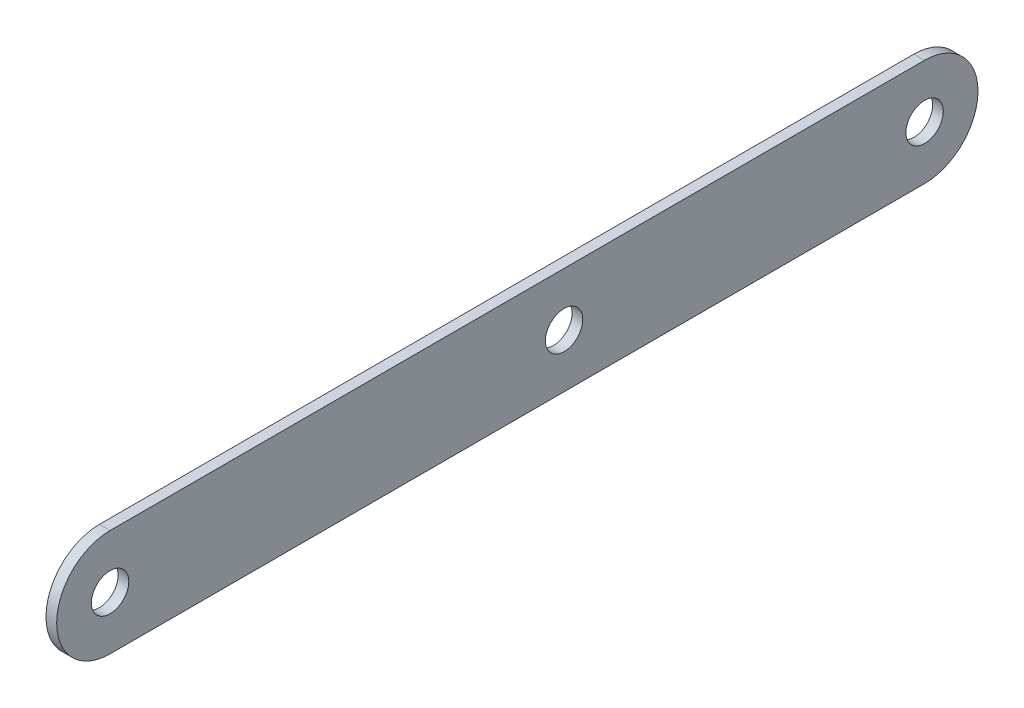
SolidWorks part; units mm, degrees
ref_plane "Спереди" through (0, 0, 0) normal (0, 0, 1) x (1, 0, 0)
ref_plane "Сверху" through (0, 0, 0) normal (0, 1, 0) x (1, 0, 0)
ref_plane "Справа" through (0, 0, 0) normal (1, 0, 0) x (0, 0, -1)
sketch "Эскиз1" plane through (0, 0, 0) normal (1, 0, 0) x (0, 0, -1)
  line L0 (0, 0) -> (305, 0) construction
  line L1 (0, 20) -> (305, 20)
  line L2 (0, -20) -> (305, -20)
  circle A0 centre (0, 0) radius 7
  arc A1 (0, 20) -> (0, -20) centre (0, 0) ccw
  circle A2 centre (305, 0) radius 7
  arc A3 (305, -20) -> (305, 20) centre (305, 0) ccw
  circle A4 centre (170, 0) radius 7
  dimension "D2" = 14
  dimension "D3" = 40
  dimension "D1" = 305
  dimension "D4" = 170
base flange "Базовая кромка1" sketch "Эскиз1" thickness 4 reverse thickness direction no parameters "D1"=1.5
sketch "Сгиб-Линии1" [suppressed] plane through (0, 0, 0) normal (0, 1, 0) x (1, 0, 0)
sketch "Граничная рамка1" [suppressed] plane through (0, 0, 0) normal (0, 1, 0) x (1, 0, 0)
sheet metal parameters "Листовой металл3" thickness 4 parameters "D1"=1.5
flat pattern "Развертка3" [suppressed]
sketch "Сгиб-Линии2" plane through (0, 0, 0) normal (0, 1, 0) x (1, 0, 0)
sketch3d "Граничная рамка2" [suppressed]
  line L0 (-20, -20, 0) -> (325, -20, 0) construction
  line L1 (-20, 20, 0) -> (325, 20, 0) construction
  line L2 (-20, -20, 0) -> (-20, 20, 0) construction
  line L3 (325, -20, 0) -> (325, 20, 0) construction
